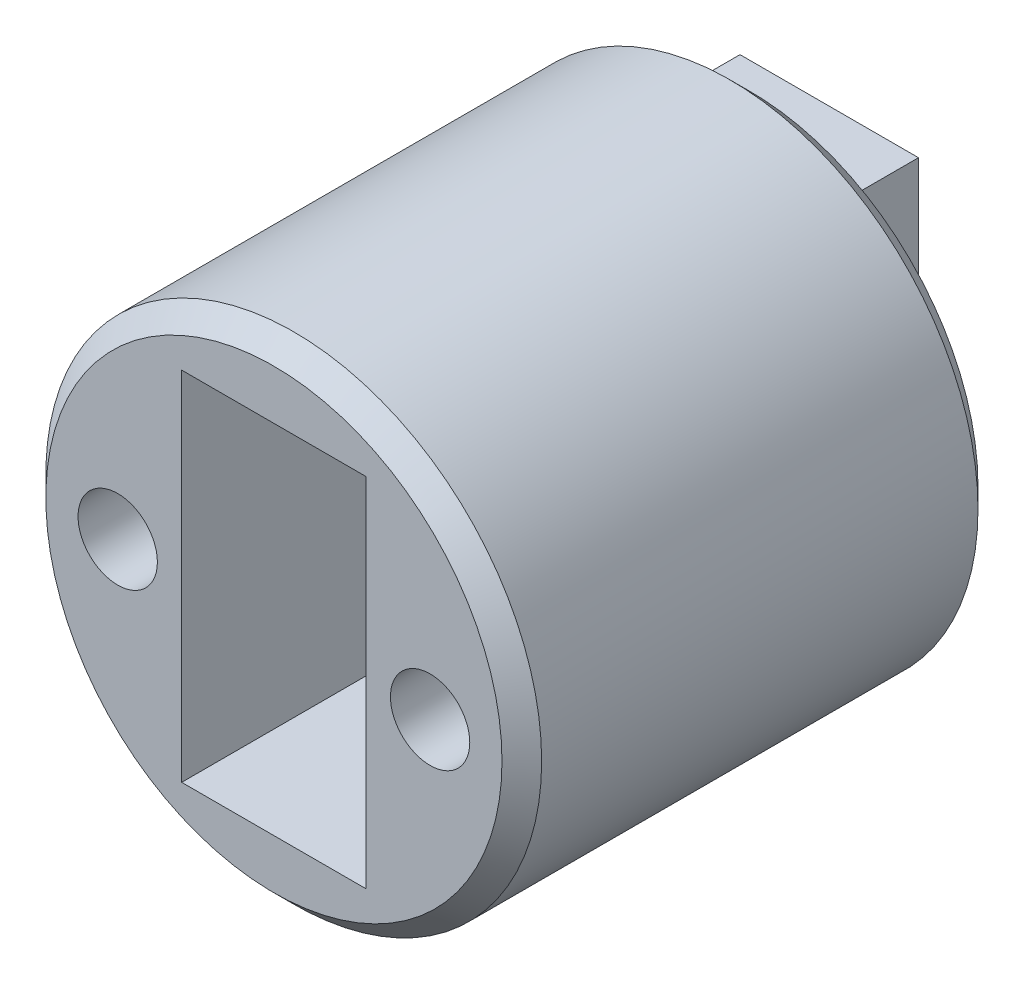
SolidWorks part; units mm, degrees
material "ABS"
ref_plane "Alzado" through (0, 0, 0) normal (0, 0, 1) x (1, 0, 0)
ref_plane "Planta" through (0, 0, 0) normal (0, 1, 0) x (1, 0, 0)
ref_plane "Vista lateral" through (0, 0, 0) normal (1, 0, 0) x (0, 0, -1)
sketch "Croquis1" plane through (0, 0, 0) normal (0, 0, 1) x (1, 0, 0)
  circle A0 centre (0, 0) radius 12.5
  dimension "D1" = 25
extrude "Saliente-Extruir1" add sketch "Croquis1" along normal blind 24
sketch "Croquis2" plane through (0, 0, 24) normal (0, 0, 1) x (1, 0, 0)
  line L1 (-4.65, 9) -> (4.65, 9)
  line L2 (-4.65, 9) -> (-4.65, -9)
  line L3 (-4.65, -9) -> (4.65, -9)
  line L4 (4.65, 9) -> (4.65, -9)
  line L5 (-4.65, 9) -> (4.65, -9) construction
  line L6 (-4.65, -9) -> (4.65, 9) construction
  point P0 (0, 0)
  dimension "D1" = 9.3
  dimension "D2" = 18
extrude "Cortar-Extruir1" cut sketch "Croquis2" against normal blind 18
sketch "Croquis3" plane through (0, 0, 0) normal (0, 0, -1) x (-1, 0, 0)
  line L1 (-4.5, 8.85) -> (4.5, 8.85)
  line L2 (-4.5, 8.85) -> (-4.5, -8.85)
  line L3 (-4.5, -8.85) -> (4.5, -8.85)
  line L4 (4.5, 8.85) -> (4.5, -8.85)
  line L5 (-4.5, 8.85) -> (4.5, -8.85) construction
  line L6 (-4.5, -8.85) -> (4.5, 8.85) construction
  point P0 (0, 0)
  dimension "D1" = 9
  dimension "D2" = 17.7
extrude "Saliente-Extruir2" add sketch "Croquis3" along normal blind 5
chamfer "Chaflán1" distance 1 angle 45 4 edges at (-4.5, 0, -5) (0, -8.85, -5) (0, 8.85, -5) (4.5, 0, -5)
chamfer "Chaflán2" distance 1 angle 45 1 edges at (12.5, 0, 0)
sketch "Croquis4" plane through (0, 0, 24) normal (0, 0, 1) x (1, 0, 0)
  line L0 (0, 17.1892) -> (0, -16.9535) construction
  circle A0 centre (-7.875, 0) radius 2
  circle A1 centre (7.875, 0) radius 2
  dimension "D2" = 4
  dimension "D1" = 15.75
extrude "Cortar-Extruir2" cut sketch "Croquis4" against normal through all
chamfer "Chaflán3" distance 1 angle 45 1 edges at (12.5, 0, 24)
sketch "Croquis5" plane through (0, 0, 6) normal (0, 0, 1) x (1, 0, 0)
  line L1 (-3, 7) -> (3, 7)
  line L2 (-3, 7) -> (-3, -7)
  line L3 (-3, -7) -> (3, -7)
  line L4 (3, 7) -> (3, -7)
  line L5 (-3, 7) -> (3, -7) construction
  line L6 (-3, -7) -> (3, 7) construction
  point P0 (0, 0)
  dimension "D1" = 14
  dimension "D2" = 6
extrude "Cortar-Extruir3" cut sketch "Croquis5" against normal through all
chamfer "Chaflán4" distance 1.95 angle 45 4 edges at (4.65, 0, 6) (0, 9, 6) (0, -9, 6) (-4.65, 0, 6)
